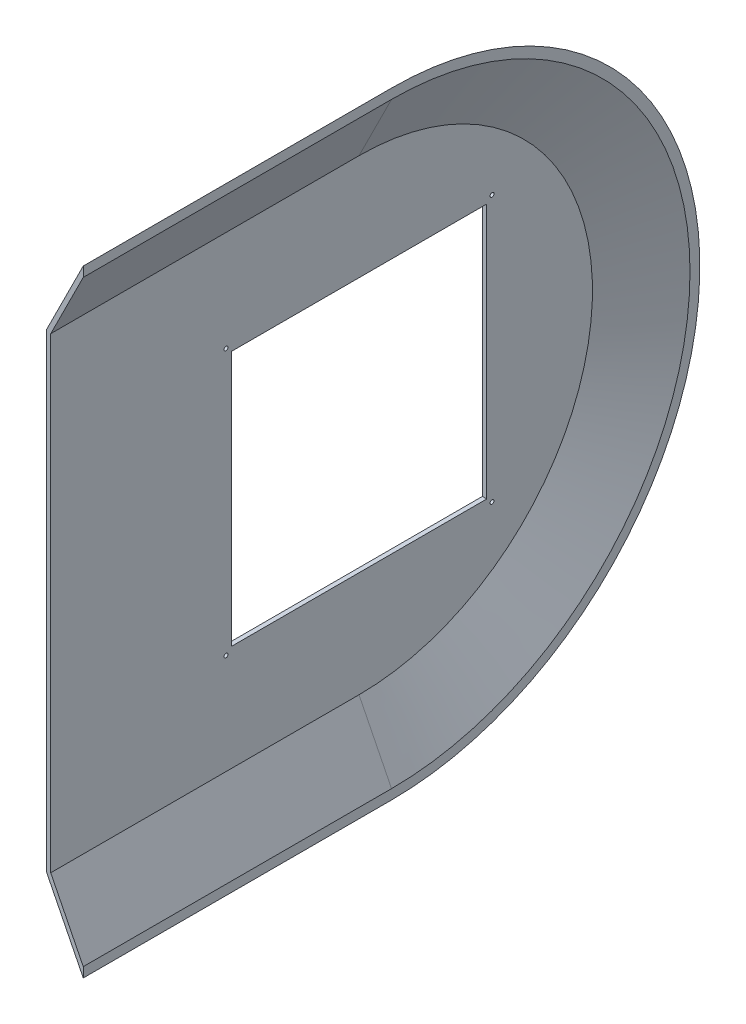
SolidWorks part; units mm, degrees
ref_plane "Plan de face" through (0, 0, 0) normal (0, 0, 1) x (1, 0, 0)
ref_plane "Plan de dessus" through (0, 0, 0) normal (0, 1, 0) x (1, 0, 0)
ref_plane "Plan de droite" through (0, 0, 0) normal (1, 0, 0) x (0, 0, -1)
sketch "Esquisse2" plane through (0, 0, 0) normal (0, 0, 1) x (1, 0, 0)
  line L0 (41.9268, 350) -> (41.9268, 0)
  line L5 (0, 266.1905) -> (41.9268, 350)
  line L6 (41.9268, 0) -> (0, 0)
  line L8 (0, 266.1905) -> (0, 0)
  dimension "D1" = 266.1905
  dimension "D2" = 350
  dimension "D3" = 153.423
  dimension "D4" = 90
revolve "Revolve1" add sketch "Esquisse2" angle 180 about L6
sketch "Sketch5" plane through (0, 0, 0) normal (0, 0, 1) x (1, 0, 0)
  line L3 (41.9268, 350) -> (0, 266.1905) construction
  line L4 (0, 266.1905) -> (41.9268, 350)
  line L5 (0, 266.1905) -> (0, -266.1905)
  line L6 (0, -266.1905) -> (41.9268, -350)
  line L7 (41.9268, -350) -> (41.9268, 350)
extrude "Boss-Extrude1" add sketch "Sketch5" along normal blind 350 contours L5 L6 L7 L4
shell "Shell2" thickness 5 removed face at (41.9268, 0, 87.5) removed face at (20.9634, 0, 350)
sketch "Sketch4" plane through (0, 0, 0) normal (-1, 0, 0) x (0, 0, 1)
  line L0 (0, -23.0597) -> (0, 23.0597) construction
  line L1 (-145, 145) -> (145, 145)
  line L2 (-145, 145) -> (-145, -145)
  line L3 (-145, -145) -> (145, -145)
  line L4 (145, 145) -> (145, -145)
  dimension "D1" = 290
  dimension "D2" = 290
  dimension "D3" = 145
  dimension "D4" = 145
extrude "Cut-Extrude1" cut sketch "Sketch4" against normal through all
sketch "Sketch7" plane through (0, 0, 0) normal (0, 0, 1) x (1, 0, 0)
  line L0 (0, 0) -> (75.7734, 0) construction
sketch "Sketch8" plane through (0, 0, 0) normal (-1, 0, 0) x (0, 0, 1)
  line L1 (-151, 151) -> (151, 151)
  line L2 (-151, 151) -> (-151, -151)
  line L3 (-151, -151) -> (151, -151)
  line L4 (151, 151) -> (151, -151)
  point P4 (0, 151)
  point P6 (151, 0)
  dimension "D1" = 302
  dimension "D2" = 302
  dimension "D3" = 0
  dimension "D4" = 0
hole_wizard "M4 Clearance Hole1" positions "Sketch11" profile "Sketch10" hole size "M4" standard "ANSI Metric"
sketch "Sketch11" plane through (0, 0, 0) normal (-1, 0, 0) x (0, 0, 1)
  point P2 (151, 151)
  point P5 (151, -151)
  point P8 (-151, -151)
  point P11 (-151, 151)
  point P15 (0, 0)
sketch "Sketch10" plane through (0, 151, 151) normal (0, 1, 0) x (0, 0, 1)
  line L0 (0, 0) -> (0, 31.3519)
  line L1 (0, 31.3519) -> (2.25, 30)
  line L2 (2.25, 30) -> (2.25, 0)
  line L5 (2.25, 0) -> (0, 0)
  line L10 (0, 31.3519) -> (-2.25, 30) construction
  line L11 (0, -6.35) -> (0, 107.95) construction
  dimension "Hole Dia." = 4.5
  dimension "Hole Depth" = 30
  dimension "Drill Angle" = 118
equation "\"D3@Sketch4\"=\"D2@Sketch4\"/2"
equation "\"D4@Sketch4\"=\"D1@Sketch4\"/2"
